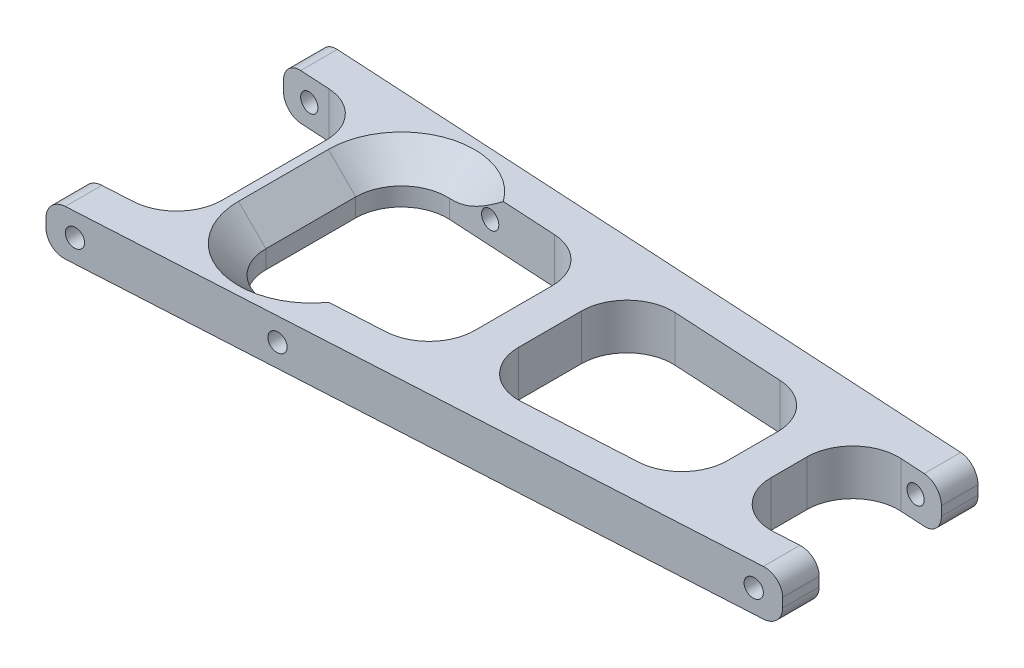
SolidWorks part; units mm, degrees
ref_plane "Front Plane" through (0, 0, 0) normal (0, 0, 1) x (1, 0, 0)
ref_plane "Top Plane" through (0, 0, 0) normal (0, 1, 0) x (1, 0, 0)
ref_plane "Right Plane" through (0, 0, 0) normal (1, 0, 0) x (0, 0, -1)
sketch "Sketch1" plane through (0, 0, 0) normal (0, 1, 0) x (1, 0, 0)
  line L0 (0, -19.0581) -> (97, -13.5881)
  line L1 (97, -13.5881) -> (97, -8.5)
  line L2 (97, 13.5881) -> (0, 19.0581)
  line L3 (0, 19.0581) -> (0, 13.97)
  line L4 (0, 0) -> (92.5552, 0) construction
  line L5 (0, 13.97) -> (12.7, 13.2538)
  line L6 (0, -13.97) -> (0, -19.0581)
  line L7 (97, -8.5) -> (84.3, -9.2162)
  line L8 (84.3, 9.2162) -> (97, 8.5)
  line L9 (12.7, 13.2538) -> (12.7, -13.2538)
  line L10 (79.22, -9.5026) -> (51.04, -11.0918)
  line L11 (17.78, 12.9674) -> (17.78, -12.9674)
  line L12 (48.5, 16.3231) -> (48.5, -16.3231) construction
  line L13 (45.96, 11.3782) -> (45.96, -11.3782)
  line L14 (45.96, -11.0918) -> (51.04, -11.0918) construction
  line L15 (51.04, 11.0918) -> (51.04, -11.0918)
  line L16 (51.04, 11.0918) -> (79.22, 9.5026)
  line L17 (79.22, 9.5026) -> (79.22, -9.5026)
  line L18 (45.96, -11.3782) -> (17.78, -12.9674)
  line L19 (84.3, 9.2162) -> (84.3, -9.2162)
  line L20 (97, 8.5) -> (97, 13.5881)
  line L22 (0, 13.97) -> (0, -13.97) construction
  line L23 (17.78, 12.9674) -> (45.96, 11.3782)
  line L24 (12.7, -13.2538) -> (0, -13.97)
  point P28 (48.5, -11.0918)
  dimension "D2" = 17
  dimension "D3" = 97
  dimension "D5" = 5.08
  dimension "D6" = 5.08
  dimension "D4" = 5.08
  dimension "D7" = 5.08
  dimension "D8" = 5.08
  dimension "D9" = 12.7
  dimension "D10" = 12.7
  dimension "D11" = 27.94
extrude "Arm" add sketch "Sketch1" along normal blind 6.35
sketch "Sketch2" plane through (0, 0, 0) normal (0, 0, 1) x (1, 0, 0)
  line L0 (30.48, 6.35) -> (30.48, 0) construction
  line L1 (0, 6.35) -> (97, 6.35) construction
  line L2 (0, 0) -> (97, 0) construction
  line L3 (0, 6.35) -> (0, 0) construction
  circle A0 centre (30.48, 3.175) radius 1.27
  dimension "D1" = 2.54
  dimension "D2" = 30.48
extrude "Cut-Extrude1" cut sketch "Sketch2" against normal through all and the other way through all
sketch "Sketch3" plane through (0, 0, 0) normal (0, 0, 1) x (1, 0, 0)
  line L0 (93.19, 6.35) -> (93.19, 0) construction
  line L1 (97, 6.35) -> (0, 6.35) construction
  line L2 (97, 0) -> (0, 0) construction
  line L3 (97, 6.35) -> (97, 0) construction
  line L4 (3.81, 6.35) -> (3.81, 0) construction
  line L5 (0, 6.35) -> (0, 0) construction
  circle A0 centre (93.19, 3.175) radius 1.27
  circle A1 centre (3.81, 3.175) radius 1.27
  dimension "D1" = 2.54
  dimension "D4" = 2.54
  dimension "D2" = 3.81
  dimension "D3" = 3.81
extrude "Cut-Extrude2" cut sketch "Sketch3" against normal through all and the other way through all
fillet "Fillet2" radius 6.35 12 edges at (12.7, 3.175, 13.2538) (12.7, 3.175, -13.2538) (84.3, 3.175, 9.2162) (45.96, 3.175, 11.3782) (51.04, 3.175, 11.0918) (17.78, 3.175, 12.9674) (17.78, 3.175, -12.9674) (84.3, 3.175, -9.2162) (79.22, 3.175, 9.5026) (51.04, 3.175, -11.0918) (79.22, 3.175, -9.5026) (45.96, 3.175, -11.3782)
fillet "Fillet3" radius 2.54 8 edges at (0, 0, 16.514) (0, 6.35, 16.514) (97, 0, -11.044) (97, 6.35, -11.044) (97, 0, 11.044) (97, 6.35, 11.044) (0, 0, -16.514) (0, 6.35, -16.514)
chamfer "Chamfer1" distance 3.81 angle 45 3 edges at (19.7681, 6.35, -10.864) (19.7681, 6.35, 10.864) (17.78, 6.35, 0)
